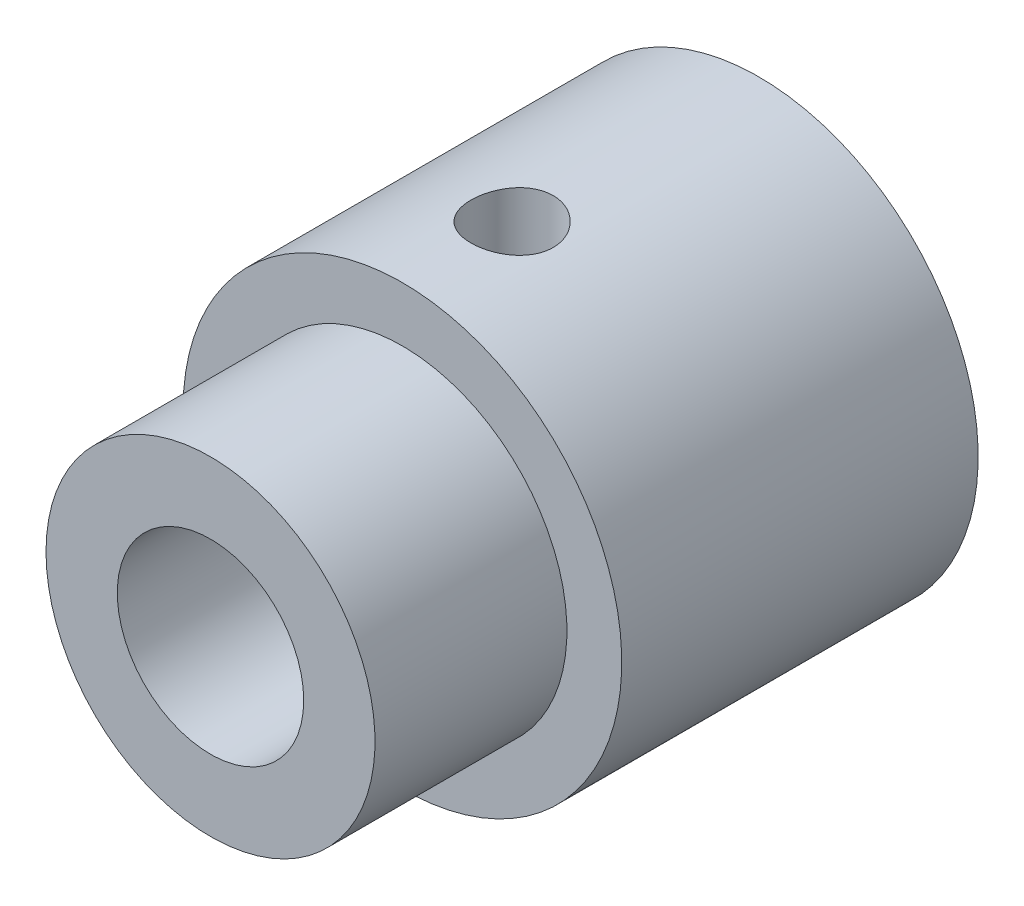
SolidWorks part; units mm, degrees
material "1060 Alloy"
ref_plane "Front Plane" through (0, 0, 0) normal (0, 0, 1) x (1, 0, 0)
ref_plane "Top Plane" through (0, 0, 0) normal (0, 1, 0) x (1, 0, 0)
ref_plane "Right Plane" through (0, 0, 0) normal (1, 0, 0) x (0, 0, -1)
sketch "Sketch1" plane through (0, 0, 0) normal (1, 0, 0) x (0, 0, -1)
  line L0 (0, 0) -> (0, 6)
  line L3 (0, 6) -> (7, 6)
  line L4 (7, 6) -> (7, 8)
  line L5 (7, 8) -> (20, 8)
  line L6 (7.5772, 0) -> (9.5, 3.2)
  line L7 (7.5772, 0) -> (0, 0)
  line L8 (9.5, 3.2) -> (20, 3.2)
  line L9 (20, 3.2) -> (20, 8)
  dimension "D3" = 7
  dimension "D4" = 6
  dimension "D5" = 13
  dimension "D6" = 8
  dimension "D7" = 3.2
  dimension "D8" = 2.5
  dimension "D9" = 121
revolve "Revolve1" add sketch "Sketch1" angle 360 about L7
sketch "Sketch2" plane through (0, 0, 0) normal (0, 1, 0) x (1, 0, 0)
  line L1 (-8, 7) -> (8, 7) construction
  circle A0 centre (0, 11) radius 1.5
  dimension "D2" = 3
  dimension "D1" = 4
extrude "Cut-Extrude1" cut sketch "Sketch2" against normal up to next and the other way up to next
hole_wizard "Tap Drill for M8x1.25 Tap2" positions "Sketch4" profile "Sketch5" hole size "M8x1.25" standard "ANSI Metric"
sketch "Sketch4" plane through (0, 0, 0) normal (0, 0, 1) x (1, 0, 0)
  point P0 (0, 0)
sketch "Sketch5" plane through (0, 0, 0) normal (1, 0, 0) x (0, -1, 0)
  line L0 (0, 0) -> (0, 12.0429)
  line L1 (0, 12.0429) -> (3.4, 10)
  line L2 (3.4, 10) -> (3.4, 0)
  line L5 (3.4, 0) -> (0, 0)
  line L10 (0, 12.0429) -> (-3.4, 10) construction
  line L11 (0, -6.35) -> (0, 107.95) construction
  dimension "Hole Dia." = 6.8
  dimension "Hole Depth" = 10
  dimension "Drill Angle" = 118
